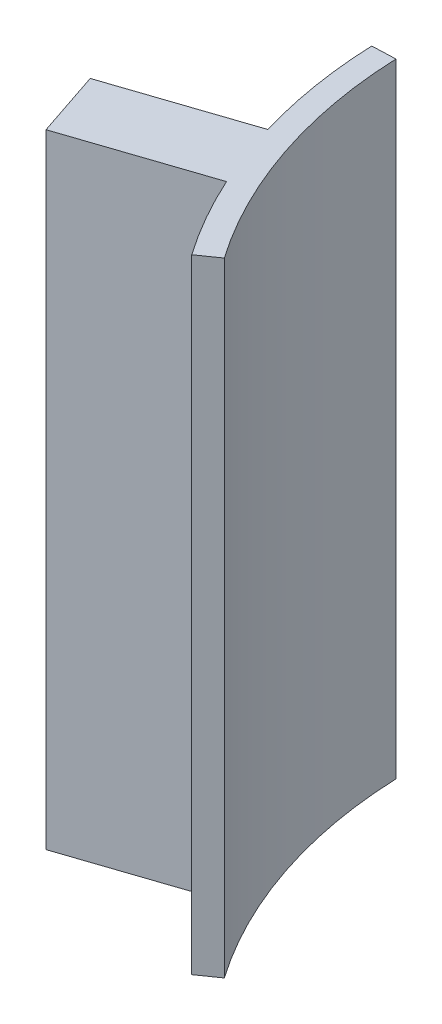
SolidWorks part; units mm, degrees
ref_plane "Front Plane" through (0, 0, 0) normal (0, 0, 1) x (1, 0, 0)
ref_plane "Top Plane" through (0, 0, 0) normal (0, 1, 0) x (1, 0, 0)
ref_plane "Right Plane" through (0, 0, 0) normal (1, 0, 0) x (0, 0, -1)
sketch "Sketch1" plane through (0, 0, 0) normal (0, 1, 0) x (1, 0, 0)
  line L0 (-61.9558, -2.3401) -> (-64.9537, -2.4533) construction
  line L1 (-61.9558, -2.3401) -> (-64.9537, -2.4533)
  line L2 (-53.3079, -37.1923) -> (-50.8475, -35.4757)
  line L4 (-76.5488, -32.6493) -> (-79.4094, -24.116)
  line L5 (-79.4094, -24.116) -> (-62.3429, -18.3947)
  line L6 (-76.5488, -32.6493) -> (-59.2024, -26.8342)
  arc A0 (-61.9558, -2.3401) -> (-50.8475, -35.4757) centre (0, 0) ccw
  arc A1 (-64.9537, -2.4533) -> (-62.3429, -18.3947) centre (0, 0) ccw
  arc A2 (-62.3429, -18.3947) -> (-64.9537, -2.4533) centre (0, 0) cw
  arc A3 (-62.3429, -18.3947) -> (-64.9537, -2.4533) centre (0, 0) cw
  arc A4 (-59.2024, -26.8342) -> (-53.3079, -37.1923) centre (0, 0) ccw
  arc A5 (-53.3079, -37.1923) -> (-59.2024, -26.8342) centre (0, 0) cw
  arc A6 (-53.3079, -37.1923) -> (-59.2024, -26.8342) centre (0, 0) cw
  point P13 (-77.9791, -28.3826)
  dimension "D1" = 4.5
extrude "Boss-Extrude1" add sketch "Sketch1" along normal blind 80 contours L6 A4 L2 A0 L1 A1 L5 L4 region at (-65.4003, 0, 23.2741)
sketch "Sketch3" plane through (2.1058, 0, 6.2814) normal (0.3179, 0, 0.9481) x (0.9481, 0, -0.3179)
  line L1 (-82.9566, 80) -> (-75.4566, 80) construction
  line L2 (-82.9566, 80) -> (-82.9566, 55) construction
  line L3 (-82.9566, 55) -> (-75.4566, 55) construction
  line L4 (-75.4566, 80) -> (-75.4566, 55) construction
  line L5 (-82.9566, 0) -> (-145.9366, 0) construction
  line L6 (-82.9566, 0) -> (-82.9566, 25) construction
  line L7 (-82.9566, 25) -> (-145.9366, 25) construction
  line L8 (-145.9366, 0) -> (-145.9366, 25) construction
  line L9 (-82.9566, 0) -> (-75.4566, 0) construction
  line L10 (-82.9566, 0) -> (-82.9566, 25) construction
  line L11 (-82.9566, 25) -> (-75.4566, 25) construction
  line L12 (-75.4566, 0) -> (-75.4566, 25) construction
  dimension "D1" = 7.5
  dimension "D2" = 25
  dimension "D3" = 25
